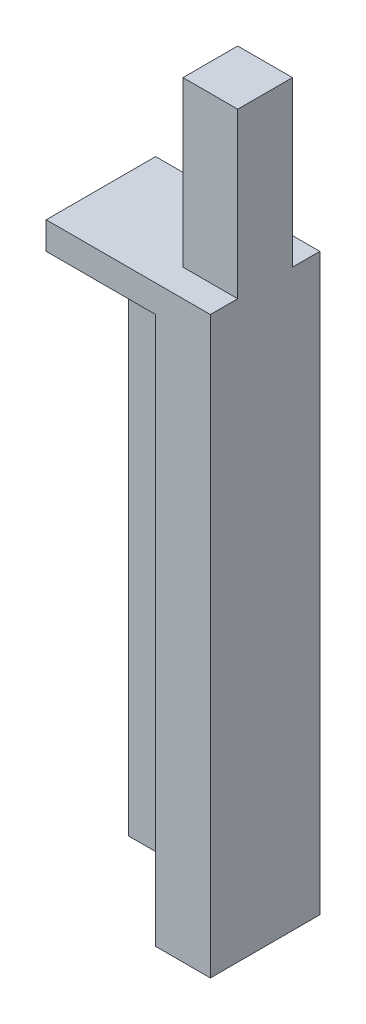
SolidWorks part; units mm, degrees
ref_plane "Front Plane" through (0, 0, 0) normal (0, 0, 1) x (1, 0, 0)
ref_plane "Top Plane" through (0, 0, 0) normal (0, 1, 0) x (1, 0, 0)
ref_plane "Right Plane" through (0, 0, 0) normal (1, 0, 0) x (0, 0, -1)
sketch "Sketch3" plane through (0, 0, 0) normal (0, 0, 1) x (1, 0, 0)
  line L0 (0, 0) -> (0, -5)
  line L1 (0, -5) -> (20, -5)
  line L2 (20, -5) -> (20, -25)
  line L3 (0, 0) -> (20, 0)
  line L4 (20, 0) -> (20, 30)
  line L5 (20, 30) -> (30, 30)
  line L6 (30, 30) -> (30, -25)
  line L7 (30, -25) -> (20, -25)
  dimension "D1" = 20
  dimension "D2" = 20
  dimension "D3" = 20
  dimension "D4" = 5
  dimension "D5" = 10
  dimension "D6" = 55
extrude "Boss-Extrude3" add sketch "Sketch3" along normal blind 10
sketch "Sketch4" plane through (0, 0, 0) normal (0, 0, -1) x (-1, 0, 0)
  line L5 (0, 0) -> (-30, 0)
  line L6 (0, 0) -> (0, -25)
  line L7 (0, -25) -> (-30, -25)
  line L8 (-30, 0) -> (-30, -25)
extrude "Boss-Extrude4" add sketch "Sketch4" along normal blind 5
sketch "Sketch5" plane through (0, 0, 10) normal (0, 0, 1) x (1, 0, 0)
  line L0 (0, 0) -> (0, -5)
  line L1 (0, -5) -> (20, -5)
  line L2 (20, -5) -> (20, -25)
  line L3 (20, -25) -> (30, -25)
  line L4 (30, -25) -> (30, 0)
  line L5 (30, 0) -> (0, 0)
extrude "Boss-Extrude5" add sketch "Sketch5" along normal blind 5
sketch "Sketch6" plane through (0, -25, 0) normal (0, -1, 0) x (1, 0, 0)
  line L0 (20, 15) -> (20, 0)
  line L1 (20, 0) -> (30, 0) construction
  line L2 (20, 0) -> (0, 0)
  line L3 (0, 0) -> (0, -5)
  line L4 (0, -5) -> (30, -5)
  line L5 (30, -5) -> (30, 15)
  line L6 (30, 15) -> (20, 15)
extrude "Boss-Extrude6" add sketch "Sketch6" along normal up to surface (80 mm away)
